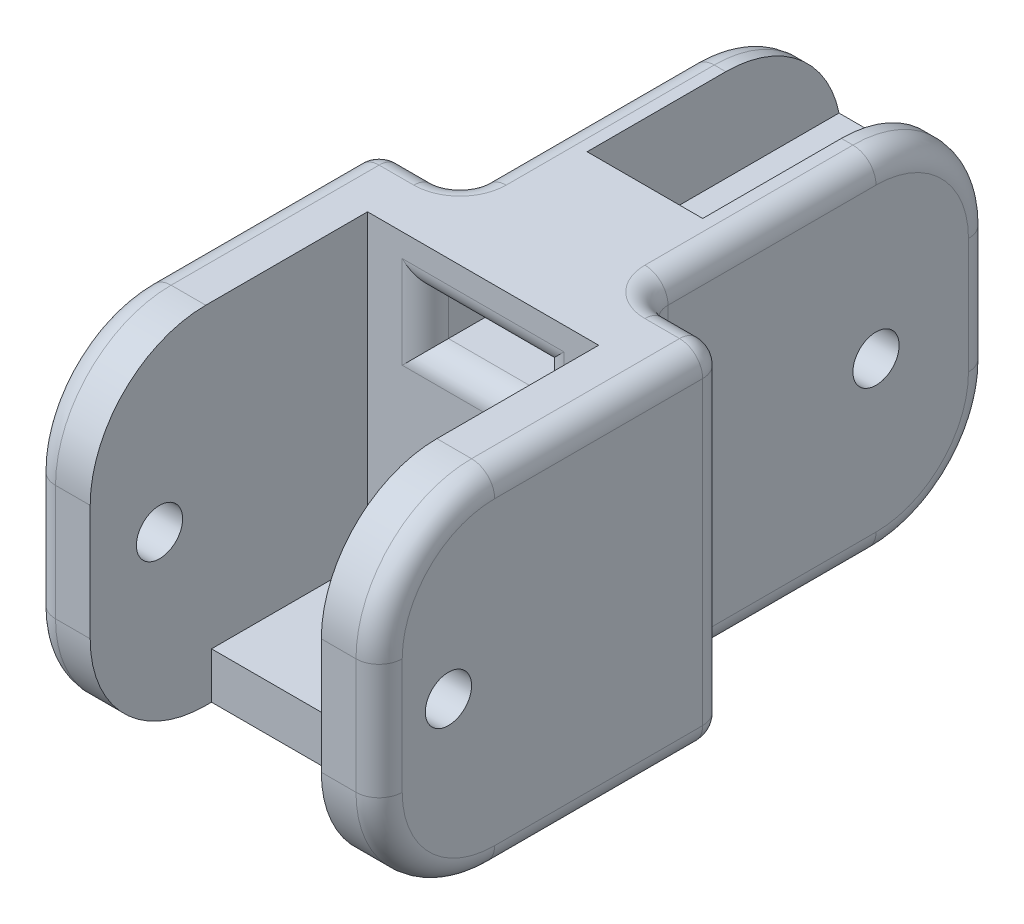
SolidWorks part; units mm, degrees
ref_plane "Front Plane" through (0, 0, 0) normal (0, 0, 1) x (1, 0, 0)
ref_plane "Top Plane" through (0, 0, 0) normal (0, 1, 0) x (1, 0, 0)
ref_plane "Right Plane" through (0, 0, 0) normal (1, 0, 0) x (0, 0, -1)
sketch "Base Sketch" plane through (0, 0, 0) normal (0, 0, 1) x (1, 0, 0)
  line L1 (-7.5, 7.5) -> (7.5, 7.5)
  line L2 (-7.5, 7.5) -> (-7.5, -7.5)
  line L3 (-7.5, -7.5) -> (7.5, -7.5)
  line L4 (7.5, 7.5) -> (7.5, -7.5)
  line L5 (-7.5, 7.5) -> (7.5, -7.5) construction
  line L6 (-7.5, -7.5) -> (7.5, 7.5) construction
  point P0 (0, 0)
  dimension "D1" = 15
  dimension "D2" = 15
extrude "Base Sketch Extrude" add sketch "Base Sketch" along normal blind 30
sketch "Center Nub Cutout Sketch" plane through (0, 0, 0) normal (0, 0, 1) x (1, 0, 0)
  line L0 (0, 0) -> (0, 10.3723) construction
  line L1 (-7.5, -7.5) -> (7.5, -7.5) construction
  line L2 (7.5, 7.5) -> (4, 7.5)
  line L3 (7.5, 7.5) -> (7.5, -7.5)
  line L4 (7.5, -7.5) -> (4, -7.5)
  line L5 (4, 7.5) -> (4, -7.5)
  line L6 (-7.5, -7.5) -> (-4, -7.5)
  line L7 (-4, 7.5) -> (-4, -7.5)
  line L8 (-7.5, 7.5) -> (-4, 7.5)
  line L9 (-7.5, 7.5) -> (-7.5, -7.5)
  dimension "D1" = 4
extrude "Hinge Nub Extruded Cut" cut sketch "Center Nub Cutout Sketch" along normal blind 15
sketch "Hinge Cutout Sketch" plane through (0, 0, 30) normal (0, 0, 1) x (1, 0, 0)
  line L0 (0, 0) -> (0, 10.344) construction
  line L1 (7.5, 7.5) -> (-7.5, 7.5) construction
  line L2 (-5, 7.5) -> (5, 7.5)
  line L3 (-5, 7.5) -> (-5, -7.5)
  line L4 (-5, -7.5) -> (5, -7.5)
  line L5 (5, 7.5) -> (5, -7.5)
  line L6 (-7.5, -7.5) -> (7.5, -7.5) construction
  dimension "D1" = 10
extrude "Hinge Cutout Extruded Cut" cut sketch "Hinge Cutout Sketch" against normal blind 12
sketch "Hinge Hole Sketch" plane through (7.5, 0, 0) normal (1, 0, 0) x (0, 0, -1)
  line L0 (0, 0) -> (-30, 0) construction
  line L1 (-30, -7.5) -> (-30, 7.5) construction
  line L2 (0, 7.5) -> (0, -7.5) construction
  circle A0 centre (-5, 0) radius 1
  circle A1 centre (-27, 0) radius 1
  dimension "D1" = 2
  dimension "D2" = 3
  dimension "D3" = 5
extrude "Hinge Hole Extruded Cut" cut sketch "Hinge Hole Sketch" against normal through all
fillet "Corner Fillets" radius 5 6 edges at (-6.25, -7.5, 30) (-6.25, 7.5, 30) (6.25, -7.5, 30) (6.25, 7.5, 30) (0, -7.5, 0) (0, 7.5, 0)
fillet "Style Fillets" radius 1 28 edges at (-7.5, -7.5, 20) (-7.5, -6.0355, 28.5355) (-7.5, 0, 30) (-7.5, 6.0355, 28.5355) (7.5, -7.5, 20) (7.5, -6.0355, 28.5355) (7.5, 0, 30) (7.5, 6.0355, 28.5355) (-4, -7.5, 10) (-4, -6.0355, 1.4645) (-4, 0, 0) (-4, 6.0355, 1.4645) (4, -7.5, 10) (4, -6.0355, 1.4645) (4, 0, 0) (4, 6.0355, 1.4645) (5.75, -7.5, 15) (7.5, 0, 15) (5.75, 7.5, 15) (-7.5, 0, 15) (-5.75, -7.5, 15) (-5.75, 7.5, 15) (-7.5, 7.5, 20) (7.5, 7.5, 20) (-4, 7.5, 10) (4, 7.5, 10) (-4, 0, 15) (4, 0, 15)
sketch "Routing Holes Sketch" plane through (0, 0, 0) normal (0, 0, 1) x (1, 0, 0)
  line L0 (0, 0) -> (12.4478, 0) construction
  line L1 (0, 0) -> (0, 10.921) construction
  line L2 (5, 7.5) -> (-5, 7.5) construction
  line L3 (-2.5, 5.5) -> (2.5, 5.5)
  line L4 (-2.5, 5.5) -> (-2.5, 3.5)
  line L5 (-2.5, 3.5) -> (2.5, 3.5)
  line L6 (2.5, 5.5) -> (2.5, 3.5)
  line L7 (2.5, -5.5) -> (2.5, -3.5)
  line L8 (-2.5, -3.5) -> (2.5, -3.5)
  line L9 (-2.5, -5.5) -> (-2.5, -3.5)
  line L10 (-2.5, -5.5) -> (2.5, -5.5)
  dimension "D1" = 5
  dimension "D2" = 2
  dimension "D3" = 2
extrude "Routing Holes Extruded Cut" cut sketch "Routing Holes Sketch" along normal through all
sketch "Sketch1" plane through (0, 0, 18) normal (0, 0, 1) x (1, 0, 0)
  line L0 (5, -7.5) -> (5, 7.5) construction
  line L1 (-5, -7.5) -> (5, -7.5)
  line L2 (-5, -7.5) -> (-5, -5.5)
  line L3 (-5, -5.5) -> (5, -5.5)
  line L4 (5, -7.5) -> (5, -5.5)
  line L5 (2.5, -5.5) -> (-2.5, -5.5) construction
extrude "Backing Extrude" add sketch "Sketch1" along normal blind 6.75
sketch "Extra Routing Cut Sketch" plane through (0, 7.5, 0) normal (0, 1, 0) x (1, 0, 0)
  line L1 (-2.5, -1) -> (2.5, -1)
  line L2 (-2.5, -1) -> (-2.5, -11)
  line L3 (-2.5, -11) -> (2.5, -11)
  line L4 (2.5, -1) -> (2.5, -11)
  point P5 (0, 0)
  dimension "D1" = 10
extrude "Extra Routing Extruded Cut" cut sketch "Extra Routing Cut Sketch" against normal up to surface (4 mm away) up to face at (0, 3.5, 9.0505)
fillet "Routing Fillets" radius 1 9 edges at (0, -3.5, 0.101) (2.5, -4.5, 18) (0, -3.5, 18) (-2.5, -4.5, 18) (2.5, 4.5, 18) (0, 3.5, 18) (-2.5, 4.5, 18) (0, 5.5, 18) (0, 5.5, 11)
